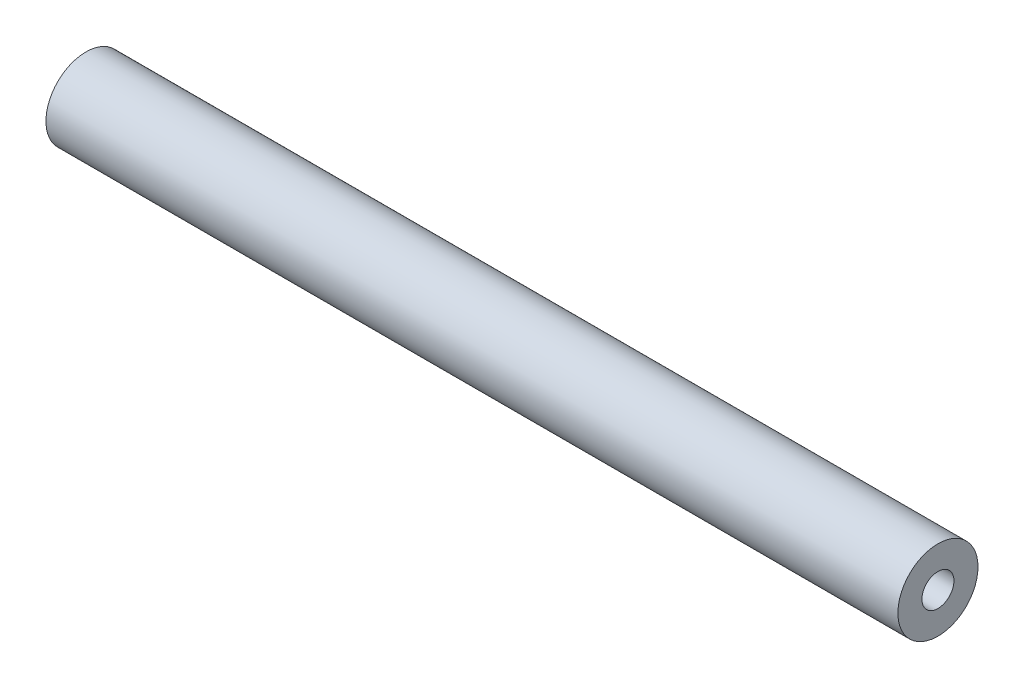
SolidWorks part; units mm, degrees
ref_plane "Alzado" through (0, 0, 0) normal (0, 0, 1) x (1, 0, 0)
ref_plane "Planta" through (0, 0, 0) normal (0, 1, 0) x (1, 0, 0)
ref_plane "Vista lateral" through (0, 0, 0) normal (1, 0, 0) x (0, 0, -1)
sketch "Croquis1" plane through (0, 0, 0) normal (0, 1, 0) x (1, 0, 0)
  line L0 (53.175, 0) -> (-53.175, 0)
  line L1 (-53.175, 0) -> (-53.175, 5)
  line L2 (-53.175, 5) -> (-10, 5)
  line L3 (-10, 5) -> (9.995, 5)
  line L4 (53.175, 5) -> (9.995, 5)
  line L5 (53.175, 0) -> (53.175, 5)
  point P4 (0, 0)
  dimension "D1" = 106.35
  dimension "D2" = 5
  dimension "D3" = 43.175
  dimension "D5" = 5
revolve "Revolución1" add sketch "Croquis1" angle 360 about L0 region at (0, 0, -2.5)
sketch "Croquis2" plane through (-53.175, 0, 0) normal (-1, 0, 0) x (0, 0, 1)
  circle A0 centre (0, 0) radius 2
  dimension "D1" = 4
extrude "Cortar-Extruir1" cut sketch "Croquis2" against normal blind 10
ref_plane "Plano1" through (3.175, 0, 0) normal (-1, 0, 0) x (0, 0, 1)
mirror "Simetría1" about plane through (3.175, 0, 0) normal (-1, 0, 0) of "Cortar-Extruir1"
